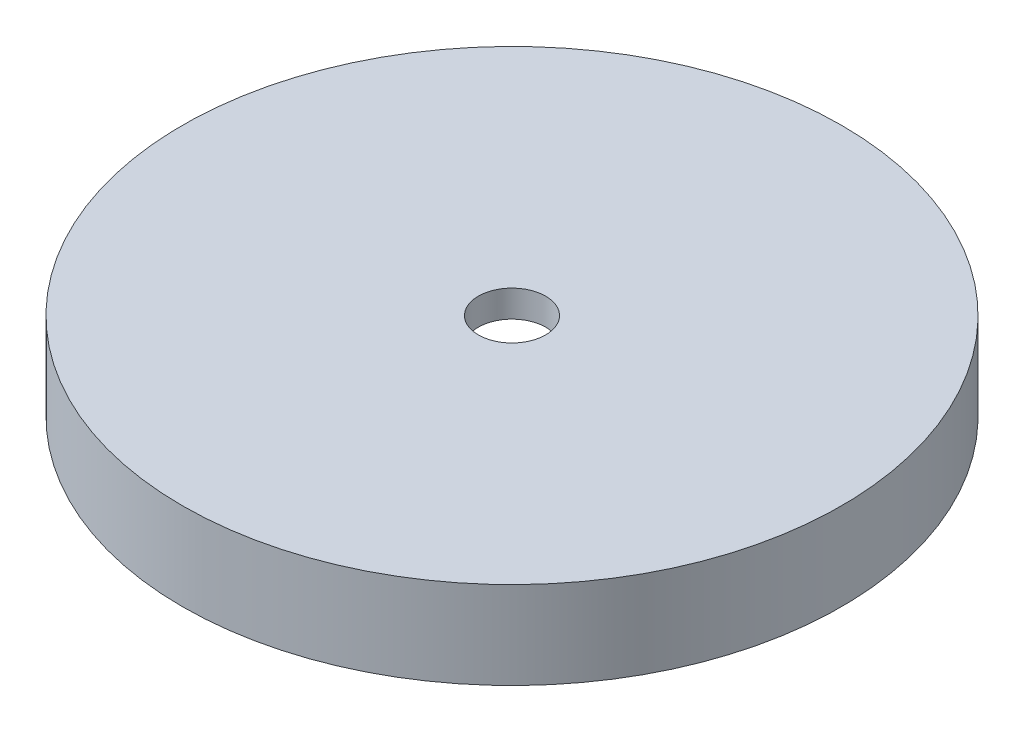
SolidWorks part; units mm, degrees
ref_plane "Front Plane" through (0, 0, 0) normal (0, 0, 1) x (1, 0, 0)
ref_plane "Top Plane" through (0, 0, 0) normal (0, 1, 0) x (1, 0, 0)
ref_plane "Right Plane" through (0, 0, 0) normal (1, 0, 0) x (0, 0, -1)
sketch "Sketch1" plane through (0, 0, 0) normal (0, 1, 0) x (1, 0, 0)
  circle A0 centre (0, 0) radius 18.5
  circle A1 centre (0, 0) radius 24.5
  dimension "D1" = 37
  dimension "D2" = 6
extrude "Boss-Extrude1" add sketch "Sketch1" along normal blind 4.5
sketch "Sketch2" plane through (0, 4.5, 0) normal (0, 1, 0) x (1, 0, 0)
  circle A1 centre (0, 0) radius 24.5
  circle A2 centre (0, 0) radius 24.5
  dimension "D1" = 0
extrude "Boss-Extrude2" add sketch "Sketch2" along normal blind 2
sketch "Sketch3" plane through (0, 0, 0) normal (0, -1, 0) x (1, 0, 0)
  circle A1 centre (0, 0) radius 21.25 construction
  circle A3 centre (0, 0) radius 2.5
  dimension "D1" = 5
  dimension "D2" = 42.5
extrude "Cut-Extrude1" cut sketch "Sketch3" against normal through all
